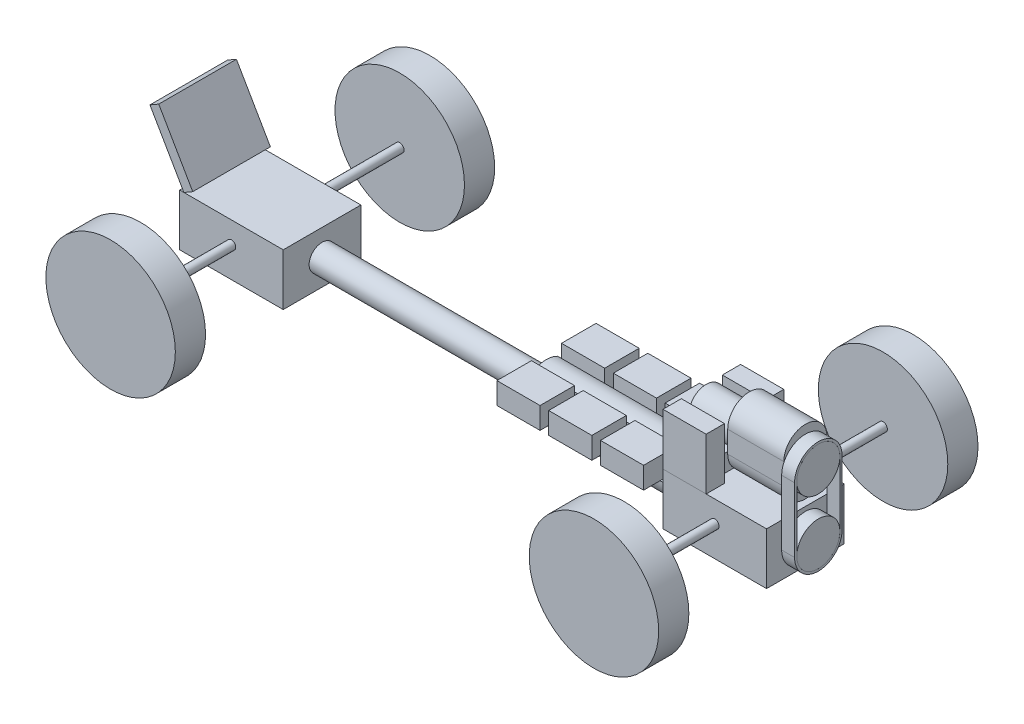
SolidWorks part; units mm, degrees
ref_plane "Front Plane" through (0, 0, 0) normal (0, 0, 1) x (1, 0, 0)
ref_plane "Top Plane" through (0, 0, 0) normal (0, 1, 0) x (1, 0, 0)
ref_plane "Right Plane" through (0, 0, 0) normal (1, 0, 0) x (0, 0, -1)
sketch "Sketch1" plane through (0, 0, 0) normal (0, 1, 0) x (1, 0, 0)
  line L1 (-1422.4, -850.9) -> (1422.4, -850.9) construction
  line L2 (-1422.4, -850.9) -> (-1422.4, 850.9) construction
  line L3 (-1422.4, 850.9) -> (1422.4, 850.9) construction
  line L4 (1422.4, -850.9) -> (1422.4, 850.9) construction
  line L5 (-1422.4, -850.9) -> (1422.4, 850.9) construction
  line L6 (-1422.4, 850.9) -> (1422.4, -850.9) construction
  line L7 (-1727.2, -228.6) -> (-1117.6, -228.6)
  line L8 (-1727.2, -228.6) -> (-1727.2, 228.6)
  line L9 (-1727.2, 228.6) -> (-1117.6, 228.6)
  line L10 (-1117.6, -228.6) -> (-1117.6, 228.6)
  line L11 (-1727.2, -228.6) -> (-1117.6, 228.6) construction
  line L12 (-1727.2, 228.6) -> (-1117.6, -228.6) construction
  line L13 (1117.6, -228.6) -> (1727.2, -228.6)
  line L14 (1117.6, -228.6) -> (1117.6, 228.6)
  line L15 (1117.6, 228.6) -> (1727.2, 228.6)
  line L16 (1727.2, -228.6) -> (1727.2, 228.6)
  line L17 (1117.6, -228.6) -> (1727.2, 228.6) construction
  line L18 (1117.6, 228.6) -> (1727.2, -228.6) construction
  point P0 (0, 0)
  point P5 (-1422.4, 0)
  point P11 (1422.4, 0)
  dimension "D1" = 2844.8
  dimension "D2" = 1701.8
  dimension "D3" = 609.6
  dimension "D4" = 457.2
sketch "Sketch2" plane through (0, 0, 0) normal (0, 0, 1) x (1, 0, 0)
  line L0 (-1422.4, 0) -> (1422.4, 0) construction
  line L1 (-1422.4, 0) -> (1422.4, 0) construction
  line L2 (-1422.4, 0) -> (-1422.4, 381) construction
  line L3 (-1422.4, 381) -> (1422.4, 381) construction
  line L4 (1422.4, 381) -> (1422.4, 0) construction
  circle A0 centre (-1422.4, 381) radius 381
  circle A1 centre (1422.4, 381) radius 381
  point P6 (1422.4, 241.4805)
  point P9 (0, 0)
  point P10 (0, 0)
  dimension "D1" = 381
ref_plane "Plane1" through (0, 0, 850.9) normal (0, 0, 1) x (1, 0, 0)
ref_plane "Plane2" through (0, 0, -850.9) normal (0, 0, 1) x (1, 0, 0)
sketch "Sketch3" plane through (0, 0, 850.9) normal (0, 0, 1) x (1, 0, 0)
  circle A0 centre (1422.4, 381) radius 381 construction
  circle A1 centre (-1422.4, 381) radius 381 construction
  circle A2 centre (1422.4, 381) radius 381
  circle A3 centre (-1422.4, 381) radius 381
sketch "Sketch4" plane through (0, 0, -850.9) normal (0, 0, 1) x (1, 0, 0)
  circle A0 centre (1422.4, 381) radius 381 construction
  circle A1 centre (-1422.4, 381) radius 381 construction
  circle A2 centre (1422.4, 381) radius 381
  circle A3 centre (-1422.4, 381) radius 381
extrude "Boss-Extrude1" add sketch "Sketch4" along normal mid plane 177.8
extrude "Boss-Extrude2" add sketch "Sketch3" along normal mid plane 177.8 separate body contours A3 | A2
extrude "Boss-Extrude3" add sketch "Sketch1" along normal blind 304.8 from offset 203.2 separate body contours L13 L16 L15 L14 | L7 L10 L9 L8 region at (-1422.4, 0, 0) region at (1422.4, 0, 0)
sketch "Sketch5" plane through (1117.6, 0, 0) normal (-1, 0, 0) x (0, 0, 1)
  line L0 (0, 508) -> (0, 203.2) construction
  line L1 (0, 355.6) -> (0, 279.4) construction
  line L2 (0, 355.6) -> (-65.9911, 393.7) construction
  line L3 (0, 355.6) -> (65.9911, 393.7) construction
  line L4 (-228.6, 203.2) -> (228.6, 203.2)
  line L5 (228.6, 203.2) -> (228.6, 508)
  line L6 (228.6, 508) -> (-228.6, 508)
  line L7 (-228.6, 508) -> (-228.6, 203.2)
  line L8 (-228.6, 203.2) -> (228.6, 203.2) construction
  line L9 (228.6, 203.2) -> (228.6, 508) construction
  line L10 (228.6, 508) -> (-228.6, 508) construction
  line L11 (-228.6, 508) -> (-228.6, 203.2) construction
  line L12 (-228.6, 203.2) -> (228.6, 203.2)
  line L13 (228.6, 203.2) -> (228.6, 508)
  line L14 (228.6, 508) -> (-228.6, 508)
  line L15 (-228.6, 508) -> (-228.6, 203.2)
  line L16 (-228.6, 203.2) -> (228.6, 203.2) construction
  line L17 (228.6, 203.2) -> (228.6, 508) construction
  line L18 (228.6, 508) -> (-228.6, 508) construction
  line L19 (-228.6, 508) -> (-228.6, 203.2) construction
  line L20 (-65.9911, 393.7) -> (-65.9911, 478.7311)
  line L21 (65.9911, 393.7) -> (65.9911, 478.7311)
  line L22 (65.9911, 393.7) -> (139.6302, 351.1845)
  line L23 (0, 279.4) -> (73.6391, 236.8845)
  line L24 (0, 279.4) -> (-73.6391, 236.8845)
  line L25 (-65.9911, 393.7) -> (-139.6302, 351.1845)
  circle A0 centre (0, 355.6) radius 139.7 construction
  circle A1 centre (0, 355.6) radius 76.2
  arc A2 (65.9911, 478.7311) -> (-65.9911, 478.7311) centre (0, 355.6) ccw
  arc A3 (73.6391, 236.8845) -> (139.6302, 351.1845) centre (0, 355.6) ccw
  arc A4 (-139.6302, 351.1845) -> (-73.6391, 236.8845) centre (0, 355.6) ccw
  point P19 (0, 355.6)
  point P32 (0, 355.6)
  dimension "D3" = 279.4
  dimension "D4" = 152.4
  dimension "D5" = 76.2
  dimension "D1" = 0
  dimension "D2" = 0
extrude "Boss-Extrude4" add sketch "Sketch5" along normal blind 914.4 separate body contours L21 A2 L20 A1 | L23 A3 L22 A1 | L25 A4 L24 A1 | A1 region at (1117.6, 306.067, -85.7936) region at (1117.6, 454.666, 0) region at (1117.6, 355.6, 0) region at (1117.6, 306.067, 85.7936)
extrude "Boss-Extrude5" add sketch "Sketch5<3>" along normal up to surface (2235.2 mm away) separate body contours A1 up to face at (-1117.6, 355.6, 0)
sketch "Sketch5<3>" plane through (1117.6, 0, 0) normal (-1, 0, 0) x (0, 0, 1) same geometry as "Sketch5"
sketch "Sketch6" plane through (1727.2, 0, 0) normal (1, 0, 0) x (0, 0, -1)
  line L0 (0, 736.6) -> (0, 355.6) construction
  line L1 (-127, 355.6) -> (-127, 736.6)
  line L2 (127, 736.6) -> (127, 355.6)
  line L3 (139.7, 736.6) -> (139.7, 355.6)
  line L4 (-139.7, 355.6) -> (-139.7, 736.6)
  circle A0 centre (0, 355.6) radius 127
  circle A1 centre (0, 736.6) radius 127
  arc A2 (-127, 736.6) -> (127, 736.6) centre (0, 736.6) cw
  arc A3 (127, 355.6) -> (-127, 355.6) centre (0, 355.6) cw
  arc A4 (-139.7, 736.6) -> (139.7, 736.6) centre (0, 736.6) cw
  arc A5 (139.7, 355.6) -> (-139.7, 355.6) centre (0, 355.6) cw
  dimension "D1" = 254
  dimension "D2" = 381
  dimension "D3" = 381
  dimension "D4" = 12.7
extrude "Boss-Extrude6" add sketch "Sketch6" along normal blind 76.2 separate body contours A1 | A0
sketch "Sketch8" plane through (1727.2, 0, 0) normal (-1, 0, 0) x (0, 0, 1)
  line L0 (0, 673.1) -> (0, 800.1) construction
  line L1 (-127, 673.1) -> (-127, 800.1)
  line L2 (127, 673.1) -> (127, 800.1)
  arc A0 (-127, 673.1) -> (127, 673.1) centre (0, 673.1) ccw
  circle A1 centre (0, 736.6) radius 127
  circle A2 centre (0, 736.6) radius 127 construction
  arc A3 (127, 800.1) -> (-127, 800.1) centre (0, 800.1) ccw
  point P5 (0, 736.6)
  dimension "D2" = 127
  dimension "D3" = 127
  dimension "D1" = 0
extrude "Boss-Extrude8" add sketch "Sketch8" along normal blind 330.2 separate body contours A3 L1 A0 L2
sketch "Sketch9" plane through (1397, 0, 0) normal (-1, 0, 0) x (0, 0, 1)
  line L0 (0, 800.1) -> (0, 673.1) construction
  line L2 (127, 673.1) -> (127, 800.1)
  line L3 (-127, 800.1) -> (-127, 673.1)
  line L4 (127, 673.1) -> (127, 800.1) construction
  line L5 (-127, 800.1) -> (-127, 673.1) construction
  line L6 (255.5028, 736.6) -> (255.5028, 737.5355) construction
  circle A0 centre (0, 736.6) radius 101.6
  arc A2 (127, 800.1) -> (-127, 800.1) centre (0, 800.1) ccw
  arc A3 (-127, 673.1) -> (127, 673.1) centre (0, 673.1) ccw
  arc A4 (127, 800.1) -> (-127, 800.1) centre (0, 800.1) ccw construction
  arc A5 (-127, 673.1) -> (127, 673.1) centre (0, 673.1) ccw construction
  dimension "D2" = 203.2
  dimension "D1" = 0
extrude "Boss-Extrude9" add sketch "Sketch9" along normal blind 254 separate body
extrude "Boss-Extrude10" add sketch "Sketch6<3>" along normal blind 76.2 separate body contours L4 A4 L3 A5 | L1 A2 L2 A3
sketch "Sketch6<3>" plane through (1727.2, 0, 0) normal (1, 0, 0) x (0, 0, -1) same geometry as "Sketch6"
ref_plane "Plane3" through (0, 406.4, 0) normal (0, 1, 0) x (1, 0, 0)
sketch "Sketch11" plane through (0, 406.4, 0) normal (0, 1, 0) x (1, 0, 0)
  line L0 (508, -88.6601) -> (508, -291.8601)
  line L1 (508, -88.6601) -> (762, -88.6601)
  line L2 (762, -88.6601) -> (762, -291.8601)
  line L3 (203.2, -88.6601) -> (457.2, -88.6601)
  line L4 (203.2, 0) -> (1117.6, 0) construction
  line L5 (203.2, 65.9911) -> (203.2, -65.9911) construction
  line L6 (1117.6, 228.6) -> (1117.6, -228.6) construction
  line L7 (203.2, -88.6601) -> (203.2, -291.8601)
  line L12 (203.2, -291.8601) -> (457.2, -291.8601)
  line L13 (457.2, -88.6601) -> (457.2, -291.8601)
  line L14 (508, -291.8601) -> (762, -291.8601)
  line L15 (812.8, -88.6601) -> (812.8, -291.8601)
  line L16 (812.8, -88.6601) -> (1066.8, -88.6601)
  line L17 (1066.8, -88.6601) -> (1066.8, -291.8601)
  line L18 (812.8, -291.8601) -> (1066.8, -291.8601)
  line L19 (812.8, 88.6601) -> (1066.8, 88.6601)
  line L20 (1066.8, 88.6601) -> (1066.8, 291.8601)
  line L21 (812.8, 291.8601) -> (1066.8, 291.8601)
  line L22 (812.8, 88.6601) -> (812.8, 291.8601)
  line L23 (508, 88.6601) -> (762, 88.6601)
  line L24 (762, 88.6601) -> (762, 291.8601)
  line L25 (508, 291.8601) -> (762, 291.8601)
  line L26 (508, 88.6601) -> (508, 291.8601)
  line L27 (203.2, 291.8601) -> (457.2, 291.8601)
  line L28 (457.2, 88.6601) -> (457.2, 291.8601)
  line L29 (203.2, 88.6601) -> (457.2, 88.6601)
  line L30 (203.2, 88.6601) -> (203.2, 291.8601)
  dimension "D1" = 203.2
  dimension "D2" = 254
  dimension "D3" = 3
extrude "Boss-Extrude11" add sketch "Sketch11" along normal blind 127 separate body
sketch "Sketch12" plane through (0, 508, 0) normal (0, 1, 0) x (1, 0, 0)
  line L0 (1117.6, 228.6) -> (1371.6, 228.6)
  line L1 (1117.6, 228.6) -> (1727.2, 228.6) construction
  line L2 (1371.6, 228.6) -> (1371.6, 120.65)
  line L3 (1371.6, 120.65) -> (1117.6, 120.65)
  line L4 (1117.6, 120.65) -> (1117.6, 228.6)
  line L5 (1397, 0) -> (1117.6, 0) construction
  line L7 (1371.6, -120.65) -> (1117.6, -120.65)
  line L8 (1371.6, -228.6) -> (1371.6, -120.65)
  line L9 (1117.6, -228.6) -> (1371.6, -228.6)
  line L10 (1117.6, -120.65) -> (1117.6, -228.6)
  line L11 (1320.8, 120.65) -> (1320.8, -120.65)
  line L12 (1143, 120.65) -> (1143, -120.65)
  line L13 (1143, 120.65) -> (1320.8, 120.65)
  line L14 (1143, -120.65) -> (1320.8, -120.65)
  point P20 (0, 0)
  line M12 (1117.6, -228.6) -> (1727.2, -228.6)
  line M14 (1727.2, 228.6) -> (1117.6, 228.6)
  line M15 (1117.6, 228.6) -> (1117.6, -228.6)
  dimension "D1" = 254
  dimension "D2" = 107.95
  dimension "D3" = 177.8
  dimension "D4" = 50.8
extrude "Boss-Extrude12" add sketch "Sketch12" along normal blind 304.8 separate body contours L3 L2 M14 M15 | L8 L7 M12 M15 region at (1244.6, 508, -174.625) region at (1244.6, 508, 174.625)
extrude "Boss-Extrude13" add sketch "Sketch12<3>" along normal blind 101.6 contours L11 L5 L12 L7 | L5 L11 L3 L12 region at (1231.9, 508, -60.325) region at (1231.9, 508, 60.325)
sketch "Sketch12<3>" plane through (0, 508, 0) normal (0, 1, 0) x (1, 0, 0) same geometry as "Sketch12"
sketch "Sketch13" plane through (0, 0, -762) normal (0, 0, 1) x (1, 0, 0)
  circle A0 centre (-1422.4, 381) radius 25.4
  circle A1 centre (1422.4, 381) radius 25.4
  dimension "D1" = 50.8
extrude "Boss-Extrude15" add sketch "Sketch13" along normal up to surface (1524 mm away) up to face at (-1041.4, 381, 762)
sketch "Sketch15" plane through (0, 0, 228.6) normal (0, 0, 1) x (1, 0, 0)
  line L0 (-1902.2, 854.4102) -> (-1702.2, 508)
  line L1 (-1727.2, 508) -> (-1117.6, 508) construction
  line L2 (-1727.2, 508) -> (-1117.6, 508) construction
  line L3 (-1902.2, 854.4102) -> (-1850.2385, 884.4102)
  line L4 (-1850.2385, 884.4102) -> (-1650.2385, 538)
  line L5 (-1650.2385, 538) -> (-1702.2, 508)
  dimension "D1" = 60
  dimension "D2" = 400
  dimension "D3" = 60
  dimension "D4" = 25
extrude "Boss-Extrude16" add sketch "Sketch15" against normal up to surface (457.2 mm away) separate body up to face at (-1447.8, 381, -228.6)
